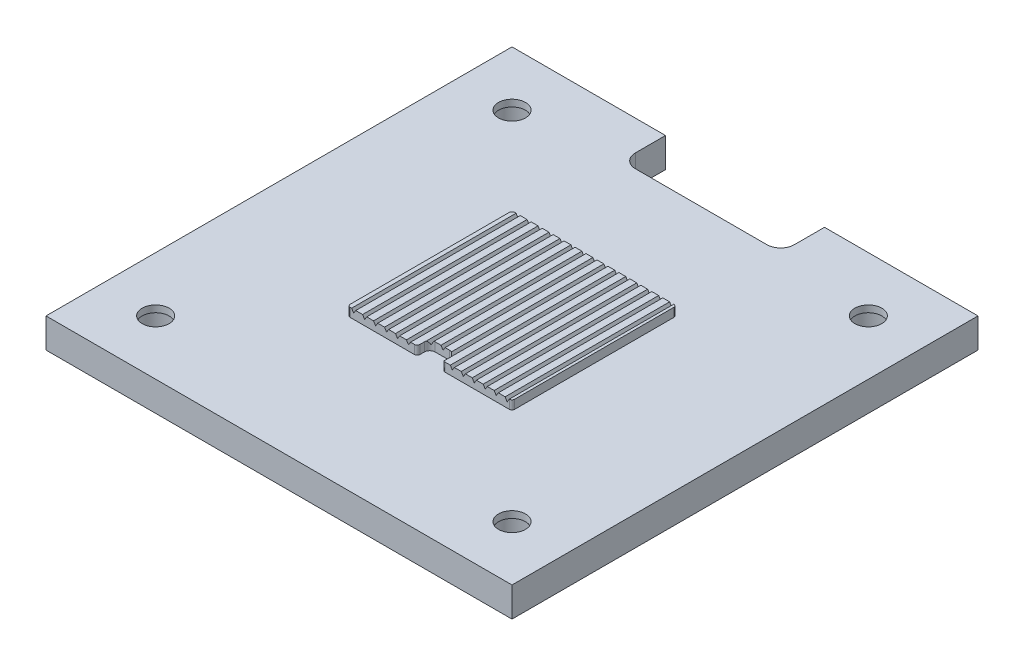
SolidWorks part; units mm, degrees
ref_plane "Front Plane" through (0, 0, 0) normal (0, 0, 1) x (1, 0, 0)
ref_plane "Top Plane" through (0, 0, 0) normal (0, 1, 0) x (1, 0, 0)
ref_plane "Right Plane" through (0, 0, 0) normal (1, 0, 0) x (0, 0, -1)
sketch "Sketch1" plane through (0, 0, 0) normal (0, 1, 0) x (1, 0, 0)
  line L0 (-7.15, 0) -> (7.15, 0) construction
  line L1 (-42.5, 42.5) -> (42.5, 42.5)
  line L2 (-42.5, 42.5) -> (-42.5, -42.5)
  line L3 (-42.5, -42.5) -> (42.5, -42.5)
  line L4 (42.5, 42.5) -> (42.5, -42.5)
  line L5 (-42.5, 42.5) -> (42.5, -42.5) construction
  line L6 (-42.5, -42.5) -> (42.5, 42.5) construction
  line L7 (0, -7.15) -> (0, 7.15) construction
  circle A0 centre (-32.5, 32.5) radius 2.4575
  circle A1 centre (-32.5, -32.5) radius 2.4575
  circle A2 centre (32.5, -32.5) radius 2.4575
  circle A3 centre (32.5, 32.5) radius 2.4575
  point P0 (0, 0)
  dimension "D3" = 4.915
  dimension "D1" = 85
  dimension "D2" = 85
  dimension "D4" = 10
  dimension "D5" = 10
extrude "Boss-Extrude1" add sketch "Sketch1" along normal blind 5.4
sketch "Sketch2" plane through (0, 0, 0) normal (0, -1, 0) x (1, 0, 0)
  line L0 (0, -55) -> (0, 55) construction
  line L1 (55, 0) -> (-55, 0) construction
  circle A0 centre (-32.5, 32.5) radius 3.969
  circle A1 centre (32.5, 32.5) radius 3.969
  circle A2 centre (32.5, -32.5) radius 3.969
  circle A3 centre (-32.5, -32.5) radius 3.969
  dimension "D1" = 7.938
extrude "Cut-Extrude1" cut sketch "Sketch2" against normal blind 4.166
sketch "Sketch5" plane through (0, 5.4, 0) normal (0, 1, 0) x (1, 0, 0)
  line L0 (42.5, 42.5) -> (-42.5, 42.5) construction
  line L1 (14.5, 42.5) -> (-14.5, 42.5)
  line L2 (14.5, 42.5) -> (14.5, 34.5)
  line L3 (14.5, 34.5) -> (-14.5, 34.5)
  line L4 (-14.5, 42.5) -> (-14.5, 34.5)
  point P6 (0, 34.5)
  dimension "D1" = 29
  dimension "D2" = 8
extrude "Cut-Extrude2" cut sketch "Sketch5" against normal blind 10
fillet "Fillet1" radius 2.5 2 edges at (-14.5, 2.7, -34.5) (14.5, 2.7, -34.5)
sketch "Sketch4" plane through (0, 5.4, 0) normal (0, 1, 0) x (1, 0, 0)
  line L0 (2.2929, -14.5) -> (2.2929, -13.7071)
  line L1 (14.5, -15) -> (2.7929, -15)
  line L2 (15, -14.5) -> (15, 14.5)
  line L3 (14.5, 15) -> (-14.5, 15)
  line L4 (-15, -14.5) -> (-15, 14.5)
  line L5 (15, -15) -> (-15, 15) construction
  line L6 (15, 15) -> (-15, -15) construction
  line L7 (1.2929, -12.7071) -> (-1.2929, -12.7071)
  line L8 (-2.2929, -13.7071) -> (-2.2929, -14.5)
  line L9 (-2.7929, -15) -> (-14.5, -15)
  arc A0 (-14.5, 15) -> (-15, 14.5) centre (-14.5, 14.5) ccw
  arc A1 (15, 14.5) -> (14.5, 15) centre (14.5, 14.5) ccw
  arc A2 (-14.5, -15) -> (-15, -14.5) centre (-14.5, -14.5) cw
  arc A3 (14.5, -15) -> (15, -14.5) centre (14.5, -14.5) ccw
  arc A4 (-2.2929, -14.5) -> (-2.7929, -15) centre (-2.7929, -14.5) cw
  arc A5 (2.2929, -14.5) -> (2.7929, -15) centre (2.7929, -14.5) ccw
  arc A6 (-1.2929, -12.7071) -> (-2.2929, -13.7071) centre (-1.2929, -13.7071) ccw
  arc A7 (2.2929, -13.7071) -> (1.2929, -12.7071) centre (1.2929, -13.7071) ccw
  point P0 (0, 0)
  point P10 (0, -12.7071)
  point P25 (-2.2929, -15)
  point P30 (-2.2929, -12.7071)
  point P33 (2.2929, -12.7071)
  dimension "D4" = 0.5
  dimension "D6" = 0.5
  dimension "D7" = 1
  dimension "D1" = 30
  dimension "D2" = 2.2929
  dimension "D3" = 4.5858
  dimension "D5" = 30
ref_plane "Plane1" through (0, 0, -15) normal (0, 0, -1) x (-1, 0, 0)
extrude "Boss-Extrude3" add sketch "Sketch4" along normal blind 1.6
sketch "Sketch10" plane through (0, 0, -15) normal (0, 0, -1) x (-1, 0, 0)
  line L0 (-14.5, 7) -> (-14.125, 6.38)
  line L1 (-14.125, 6.38) -> (-13.75, 7)
  line L2 (-13.75, 7) -> (-14.5, 7)
  line L46 (-42.5, 5.4) -> (-42.5, 0) construction
  line L47 (-12.125, 6.38) -> (-11.75, 7)
  line L48 (-11.75, 7) -> (-12.5, 7)
  line L49 (-12.5, 7) -> (-12.125, 6.38)
  line L50 (-10.125, 6.38) -> (-9.75, 7)
  line L51 (-9.75, 7) -> (-10.5, 7)
  line L52 (-10.5, 7) -> (-10.125, 6.38)
  line L53 (-8.125, 6.38) -> (-7.75, 7)
  line L54 (-7.75, 7) -> (-8.5, 7)
  line L55 (-8.5, 7) -> (-8.125, 6.38)
  line L56 (-6.125, 6.38) -> (-5.75, 7)
  line L57 (-5.75, 7) -> (-6.5, 7)
  line L58 (-6.5, 7) -> (-6.125, 6.38)
  line L59 (-4.125, 6.38) -> (-3.75, 7)
  line L60 (-3.75, 7) -> (-4.5, 7)
  line L61 (-4.5, 7) -> (-4.125, 6.38)
  line L62 (-2.125, 6.38) -> (-1.75, 7)
  line L63 (-1.75, 7) -> (-2.5, 7)
  line L64 (-2.5, 7) -> (-2.125, 6.38)
  line L65 (-0.125, 6.38) -> (0.25, 7)
  line L66 (0.25, 7) -> (-0.5, 7)
  line L67 (-0.5, 7) -> (-0.125, 6.38)
  line L68 (1.875, 6.38) -> (2.25, 7)
  line L69 (2.25, 7) -> (1.5, 7)
  line L70 (1.5, 7) -> (1.875, 6.38)
  line L71 (3.875, 6.38) -> (4.25, 7)
  line L72 (4.25, 7) -> (3.5, 7)
  line L73 (3.5, 7) -> (3.875, 6.38)
  line L74 (5.875, 6.38) -> (6.25, 7)
  line L75 (6.25, 7) -> (5.5, 7)
  line L76 (5.5, 7) -> (5.875, 6.38)
  line L77 (7.875, 6.38) -> (8.25, 7)
  line L78 (8.25, 7) -> (7.5, 7)
  line L79 (7.5, 7) -> (7.875, 6.38)
  line L80 (9.875, 6.38) -> (10.25, 7)
  line L81 (10.25, 7) -> (9.5, 7)
  line L82 (9.5, 7) -> (9.875, 6.38)
  line L83 (11.875, 6.38) -> (12.25, 7)
  line L84 (12.25, 7) -> (11.5, 7)
  line L85 (11.5, 7) -> (11.875, 6.38)
  line L86 (13.875, 6.38) -> (14.25, 7)
  line L87 (14.25, 7) -> (13.5, 7)
  line L88 (13.5, 7) -> (13.875, 6.38)
  dimension "D1" = 0.375
  dimension "D2" = 0.375
  dimension "D3" = 0.62
  dimension "D4" = 28
  dimension "D5" = 15
  dimension "D6" = 1.6
extrude "Cut-Extrude5" cut sketch "Sketch10" against normal blind 30
